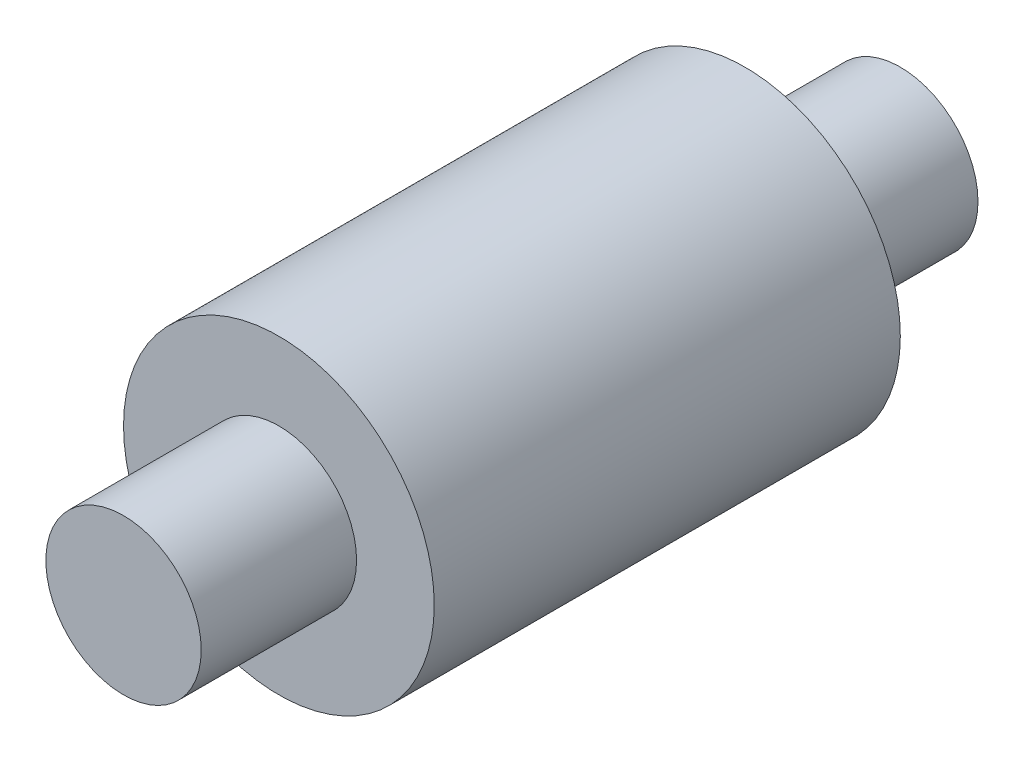
SolidWorks part; units mm, degrees
ref_plane "Alzado" through (0, 0, 0) normal (0, 0, 1) x (1, 0, 0)
ref_plane "Planta" through (0, 0, 0) normal (0, 1, 0) x (1, 0, 0)
ref_plane "Vista lateral" through (0, 0, 0) normal (1, 0, 0) x (0, 0, -1)
sketch "Croquis1" plane through (0, 0, 0) normal (0, 0, 1) x (1, 0, 0)
  circle A0 centre (0, 0) radius 1
  dimension "D1" = 2
extrude "Saliente-Extruir1" add sketch "Croquis1" along normal blind 5 and the other way blind 5
sketch "Croquis2" plane through (0, 0, 0) normal (0, 0, 1) x (1, 0, 0)
  circle A0 centre (0, 0) radius 2
  dimension "D1" = 4
extrude "Saliente-Extruir2" add sketch "Croquis2" along normal blind 3 and the other way blind 3
